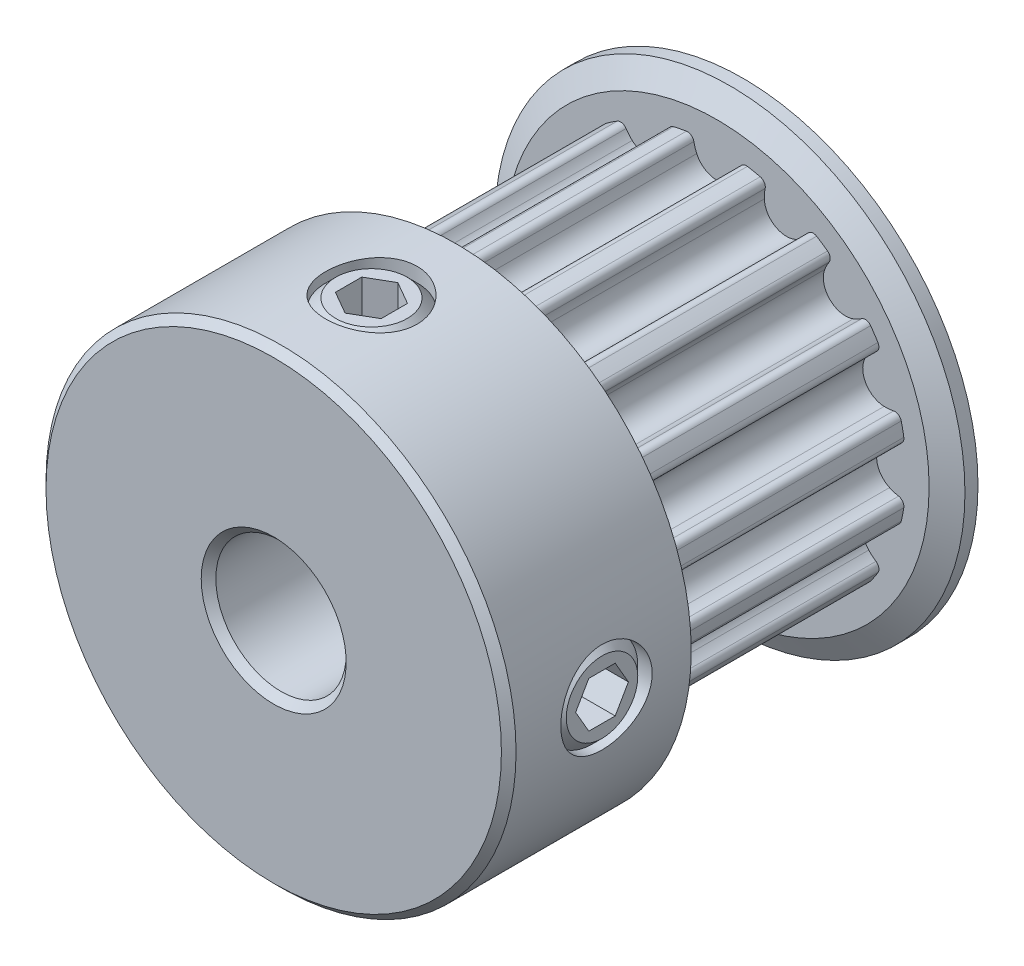
SolidWorks part; units mm, degrees
ref_plane "Front Plane" through (0, 0, 0) normal (0, 0, 1) x (1, 0, 0)
ref_plane "Top Plane" through (0, 0, 0) normal (0, 1, 0) x (1, 0, 0)
ref_plane "Right Plane" through (0, 0, 0) normal (1, 0, 0) x (0, 0, -1)
sketch "Sketch1" plane through (0, 0, 0) normal (0, 0, 1) x (1, 0, 0)
  line L1 (-2.553, 6.1245) -> (2.553, 6.1245) construction
  line L4 (0, 0) -> (0, 6.1245) construction
  line L5 (0, 6.1245) -> (0, 12.0663) construction
  line L6 (0, 7.6455) -> (2.9417, 7.0569) construction
  line L7 (2.9417, 7.0569) -> (3.8741, 6.6682) construction
  line L8 (2.9417, 7.0569) -> (2.553, 6.1245) construction
  line L9 (-2.9417, 7.0569) -> (-2.553, 6.1245) construction
  line L10 (-2.7951, 6.7052) -> (-3.7579, 9.015)
  line L11 (-3.7579, 9.015) -> (3.7579, 9.015)
  line L12 (3.7579, 9.015) -> (2.7951, 6.7052)
  circle A0 centre (0, 0) radius 7.6455 construction
  circle A1 centre (0, 0) radius 9.015 construction
  circle A2 centre (0, 0) radius 7.2645 construction
  arc A3 (-0.7739, 6.6229) -> (0.7739, 6.6229) centre (0, 6.9745) ccw
  arc A4 (-0.7739, 6.6229) -> (-0.8836, 6.9694) centre (0.61, 7.2516) cw
  arc A5 (-2.7951, 6.7052) -> (-1.1695, 7.1697) centre (0, 0) cw
  arc A6 (-0.8836, 6.9694) -> (-1.1695, 7.1697) centre (-1.1292, 6.923) ccw
  arc A7 (2.7951, 6.7052) -> (1.1695, 7.1697) centre (0, 0) ccw
  arc A8 (0.8836, 6.9694) -> (1.1695, 7.1697) centre (1.1292, 6.923) cw
  arc A9 (0.7739, 6.6229) -> (0.8836, 6.9694) centre (-0.61, 7.2516) ccw
  point P6 (0, 20.9083)
  point P11 (0, 7.6455)
  point P13 (0, 9.015)
  point P14 (0, 7.2645)
  dimension "D1" = 8.842
  dimension "D2" = 4.4208
sketch "Sketch2" plane through (0, 0, 0) normal (1, 0, 0) x (0, 0, -1)
  line L0 (-9, 2.5) -> (9, 2.5)
  line L1 (-9, 2.5) -> (-9, 9.015)
  line L2 (-2, 9.015) -> (-9, 9.015)
  line L3 (-2.5, 2.5) -> (-2.5, 9.015) construction
  line L4 (-2.5, 9.015) -> (-1.5, 9.015) construction
  line L5 (-1.5, 9.015) -> (-1.5, 7.2645) construction
  line L6 (-1.5, 7.2645) -> (8, 7.2645)
  line L7 (8, 7.2645) -> (8, 9.015) construction
  line L8 (8, 9.015) -> (9, 9.015) construction
  line L9 (9, 9.015) -> (9, 2.5)
  line L10 (-9, 0) -> (9, 0) construction
  line L11 (8.5, 9.015) -> (8, 8.1398)
  line L12 (-1.5, 8.1398) -> (-2, 9.015)
  line L14 (-1.5, 8.1398) -> (-1.5, 7.2645)
  line L15 (8, 7.2645) -> (8, 8.1398)
  line L16 (8.5, 9.015) -> (9, 9.015)
  arc A0 (-1.5, 8.1398) -> (-2, 9.015) centre (-2.5161, 8.1398) ccw construction
  arc A1 (8, 8.1398) -> (8.5, 9.015) centre (9.0161, 8.1398) cw construction
  point P12 (-1.5, 8.1398)
  point P14 (-2, 9.015)
  point P20 (8, 8.1398)
  point P21 (8.5, 9.015)
  point P25 (8, 0)
  point P26 (-1.5, 0)
  dimension "D1" = 7.5
  dimension "OA" = 18
  dimension "Bore" = 5
  dimension "Inside Width" = 9.5
revolve "Revolve1" add sketch "Sketch2" angle 360 mid plane about L10
sketch "Sketch3" plane through (0, 0, 0) normal (0, 0, 1) x (1, 0, 0)
  line L6 (3.7579, 9.015) -> (-3.7579, 9.015)
  line L7 (2.7951, 6.7052) -> (3.7579, 9.015)
  line L8 (-3.7579, 9.015) -> (-2.7951, 6.7052)
  line L9 (3.7579, 9.015) -> (-3.7579, 9.015)
  line L10 (2.7951, 6.7052) -> (3.7579, 9.015)
  line L11 (-3.7579, 9.015) -> (-2.7951, 6.7052)
  arc A8 (2.7951, 6.7052) -> (1.1695, 7.1697) centre (0, 0) ccw
  arc A9 (1.1695, 7.1697) -> (0.8836, 6.9694) centre (1.1292, 6.923) ccw
  arc A10 (0.7739, 6.6229) -> (0.8836, 6.9694) centre (-0.61, 7.2516) ccw
  arc A11 (-0.7739, 6.6229) -> (0.7739, 6.6229) centre (0, 6.9745) ccw
  arc A12 (-0.8836, 6.9694) -> (-0.7739, 6.6229) centre (0.61, 7.2516) ccw
  arc A13 (-0.8836, 6.9694) -> (-1.1695, 7.1697) centre (-1.1292, 6.923) ccw
  arc A14 (-1.1695, 7.1697) -> (-2.7951, 6.7052) centre (0, 0) ccw
  arc A15 (2.7951, 6.7052) -> (1.1695, 7.1697) centre (0, 0) ccw
  arc A16 (1.1695, 7.1697) -> (0.8836, 6.9694) centre (1.1292, 6.923) ccw
  arc A17 (0.7739, 6.6229) -> (0.8836, 6.9694) centre (-0.61, 7.2516) ccw
  arc A18 (-0.7739, 6.6229) -> (0.7739, 6.6229) centre (0, 6.9745) ccw
  arc A19 (-0.8836, 6.9694) -> (-0.7739, 6.6229) centre (0.61, 7.2516) ccw
  arc A20 (-0.8836, 6.9694) -> (-1.1695, 7.1697) centre (-1.1292, 6.923) ccw
  arc A21 (-1.1695, 7.1697) -> (-2.7951, 6.7052) centre (0, 0) ccw
  dimension "D1" = 0
extrude "Cut-Extrude1" cut sketch "Sketch3" against normal up to vertex (8 mm away) from vertex up to point (0, 7.2645, -8) starting at point (0, 7.2645, 1.5)
pattern_circular "CirPattern1" count 16 over 360 about axis through (0, 0, 9) along (0, 0, 1) of "Cut-Extrude1"
sketch "Sketch4" plane through (0, 0, 0) normal (1, 0, 0) x (0, -1, 0)
  line L0 (0, -1.5) -> (0, -9) construction
  line L1 (-2.5, -9) -> (2.5, -9) construction
  line L2 (8.1398, -1.5) -> (-8.1398, -1.5) construction
  circle A0 centre (0, -5.25) radius 1.7526
extrude "Cut-Extrude2" cut sketch "Sketch4" along normal through all
ref_plane "Plane1" through (0, 0, 5.25) normal (0, 0, 1) x (1, 0, 0)
sketch "Sketch5" plane through (0, 0, 5.25) normal (0, 0, 1) x (1, 0, 0)
  line L0 (0, 0) -> (0, 9.015) construction
  line L1 (2.5, -1.3716) -> (2.5, 0)
  line L2 (2.881, -1.7526) -> (8.462, -1.7526)
  line L3 (2.5, 0) -> (9.015, 0) construction
  line L4 (2.5, 0) -> (8.843, 0)
  line L5 (8.843, 0) -> (8.843, -1.3716)
  line L6 (2.881, -1.7526) -> (2.5, -1.3716)
  line L7 (8.843, -1.3716) -> (8.462, -1.7526)
  circle A0 centre (0, 0) radius 9.015 construction
  circle A1 centre (0, 0) radius 2.5 construction
  point P2 (2.5, -1.7526)
  point P11 (8.843, -1.7526)
revolve "Revolve2" add sketch "Sketch5" angle 360 mid plane about L4
sketch "Sketch6" plane through (8.843, 5.3841, 0) normal (-1, 0, 0) x (0, -1, 0)
  line L1 (5.3841, 6.2619) -> (4.5078, 5.7559)
  line L2 (4.5078, 5.7559) -> (4.5078, 4.7441)
  line L3 (4.5078, 4.7441) -> (5.3841, 4.2381)
  line L4 (5.3841, 4.2381) -> (6.2604, 4.7441)
  line L5 (6.2604, 4.7441) -> (6.2604, 5.7559)
  line L6 (6.2604, 5.7559) -> (5.3841, 6.2619)
  circle A0 centre (5.3841, 5.25) radius 0.8763 construction
  dimension "D1" = 1.7526
extrude "Cut-Extrude3" cut sketch "Sketch6" along normal blind 1.3144
pattern_circular "CirPattern3" count 2 over 90 about axis through (0, 0, 9) along (0, 0, 1) of "Cut-Extrude2", "Revolve2", "Cut-Extrude3"
chamfer "Chamfer1" distance 0.2807 angle 45 2 edges at (2.5, 0, 9) (9.015, 0, 9)
ref_axis "Center Axis 1" through (0, 0, -9) along (0, 0, 1)
ref_plane "Contact Plane 1" through (0, 0, 9) normal (0, 0, 1) x (1, 0, 0)
ref_plane "Contact Plane 2" through (0, 0, -9) normal (0, 0, -1) x (-1, 0, 0)
equation "\"D2@Sketch1\"= \"D1@Sketch1\" / 2"
equation "\"D1@Sketch6\" = \"Set Screw@Sketch4\" / 2"
equation "\"D1@Cut-Extrude3\" = \"D1@Sketch6\"*.75"
